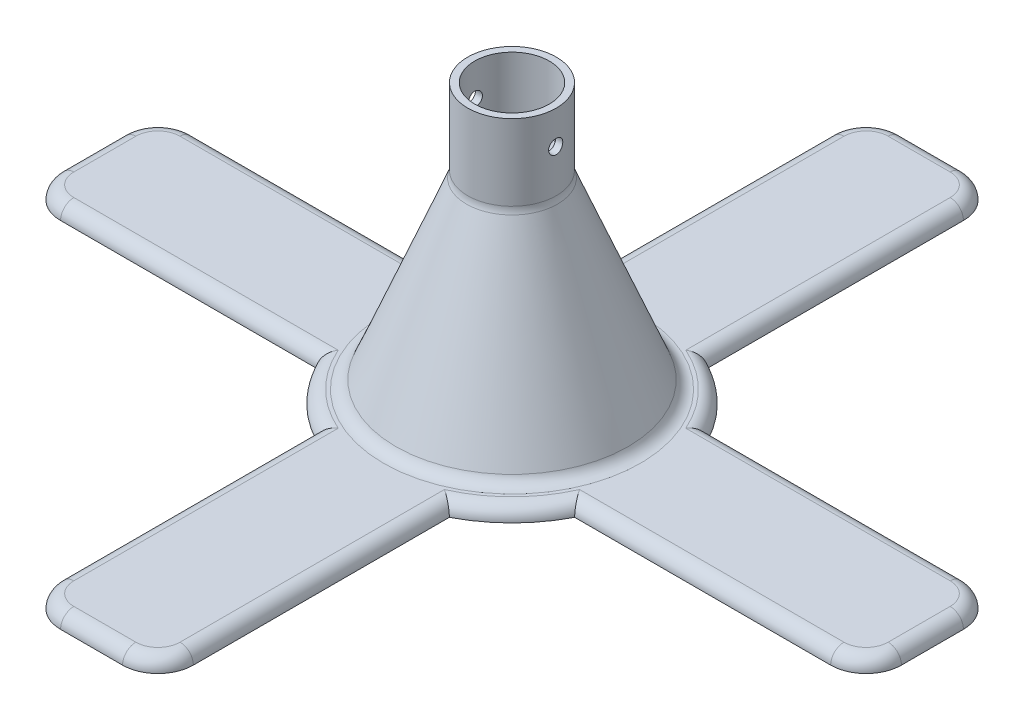
SolidWorks part; units mm, degrees
ref_plane "Front Plane" through (0, 0, 0) normal (0, 0, 1) x (1, 0, 0)
ref_plane "Top Plane" through (0, 0, 0) normal (0, 1, 0) x (1, 0, 0)
ref_plane "Right Plane" through (0, 0, 0) normal (1, 0, 0) x (0, 0, -1)
sketch "Sketch1" plane through (0, 0, 0) normal (0, 1, 0) x (1, 0, 0)
  line L0 (0, 95) -> (0, -95)
  line L1 (0, -55) -> (0, 55) construction
  line L2 (15, -29.159) -> (15, -95)
  line L3 (-95, 0) -> (95, 0)
  line L4 (-55, 0) -> (55, 0) construction
  line L5 (29.159, 15) -> (95, 15)
  line L6 (95, 15) -> (95, 0)
  line L7 (95, -15) -> (29.159, -15)
  line L8 (29.159, -15) -> (95, -15)
  line L9 (95, -15) -> (95, 0)
  line L10 (15, -95) -> (0, -95)
  line L11 (-15, -95) -> (0, -95)
  line L12 (-15, -95) -> (-15, -29.159)
  line L13 (-29.159, -15) -> (-95, -15)
  line L14 (-95, -15) -> (-95, 0)
  line L15 (-95, 15) -> (-95, 0)
  line L16 (-95, 15) -> (-29.159, 15)
  line L17 (-15, 29.159) -> (-15, 95)
  line L18 (-15, 95) -> (0, 95)
  line L19 (15, 95) -> (0, 95)
  line L20 (15, 95) -> (15, 29.159)
  circle A0 centre (0, 0) radius 32.791
  point P6 (0, 0)
  point P12 (0, 0)
  point P35 (0, 0)
  dimension "D3" = 30
  dimension "D1" = 190
  dimension "D2" = 190
  dimension "D4" = 15
  dimension "D5" = 4
extrude "Boss-Extrude1" add sketch "Sketch1" along normal blind 3 contours A0 L3 L6 L5 | A0 L7 L9 L3 | L0 A0 L3 | L3 A0 L0 | L0 A0 L3 | L3 A0 L0 | A0 L0 L18 L17 | A0 L20 L19 L0 | A0 L16 L15 L3 | A0 L3 L14 L13 | A0 L12 L11 L0 | A0 L0 L10 L2 region at (7.5708, 0, -63.2951) region at (-7.5708, 0, -63.2951) region at (13.9169, 0, -13.9169) region at (-13.9169, 0, -13.9169) region at (13.9169, 0, 13.9169) region at (-13.9169, 0, 13.9169) region at (7.5708, 0, 63.2951) region at (-7.5708, 0, 63.2951) region at (-63.2951, 0, 7.5708) region at (-63.2951, 0, -7.5708) region at (63.2951, 0, -7.5708) region at (63.2951, 0, 7.5708)
fillet "Fillet4" radius 8 8 edges at (15, 1.5, 95) (-15, 1.5, 95) (-95, 1.5, 15) (-95, 1.5, -15) (-15, 1.5, -95) (15, 1.5, -95) (95, 1.5, -15) (95, 1.5, 15)
fillet "Fillet5" radius 3 24 edges at (-12.6569, 3, 92.6569) (-15, 3, 58.0795) (-23.1867, 3, 23.1867) (-58.0795, 3, 15) (-92.6569, 3, 12.6569) (-95, 3, 0) (-92.6569, 3, -12.6569) (-58.0795, 3, -15) (-23.1867, 3, -23.1867) (-15, 3, -58.0795) (-12.6569, 3, -92.6569) (0, 3, -95) (12.6569, 3, -92.6569) (15, 3, -58.0795) (23.1867, 3, -23.1867) (58.0795, 3, -15) (92.6569, 3, -12.6569) (95, 3, 0) (92.6569, 3, 12.6569) (58.0795, 3, 15) (23.1867, 3, 23.1867) (15, 3, 58.0795) (12.6569, 3, 92.6569) (0, 3, 95)
sketch "Sketch4" plane through (0, 3, 0) normal (0, 1, 0) x (1, 0, 0)
  circle A0 centre (0, 0) radius 10
extrude "Boss-Extrude4" add sketch "Sketch4" along normal blind 60
chamfer "Chamfer2" distance 17 angle 68 1 edges at (0, 3, 10) first distance on face at (0, 3, 10)
fillet "Fillet7" radius 4 1 edges at (0, 45.0765, 10)
sketch "Sketch5" plane through (0, 0, 0) normal (0, -1, 0) x (1, 0, 0)
  circle A0 centre (0, 0) radius 15
  dimension "D1" = 30
extrude "Cut-Extrude1" cut sketch "Sketch5" against normal blind 32
fillet "Fillet8" radius 3 1 edges at (0, 3, 27)
sketch "Sketch6" plane through (0, 63, 0) normal (0, 1, 0) x (1, 0, 0)
  circle A0 centre (0, 0) radius 8.43
extrude "Cut-Extrude2" cut sketch "Sketch6" against normal blind 15
fillet "Fillet9" radius 4 1 edges at (0, 32, -15)
sketch "Sketch8" plane through (0, 0, 0) normal (1, 0, 0) x (0, 0, -1)
  line L0 (0, 63) -> (0, 48)
  line L1 (10, 63) -> (-10, 63) construction
  line L2 (0, 34.7644) -> (0, -34.7644) construction
  line L3 (0, 63) -> (0, 48) construction
  line L4 (0, 55.5) -> (1.6, 55.5)
  circle A0 centre (0, 55.5) radius 1.6
  dimension "D1" = 15
  dimension "D2" = 1.6
extrude "Cut-Extrude3" cut sketch "Sketch8" against normal blind 15 and the other way blind 15 contours L0 A0 | L4 A0 L0 | L0 A0 L4 region at (0, 56.1791, -0.6791) region at (0, 55.5, 0.6791) region at (0, 54.8209, -0.6791)
